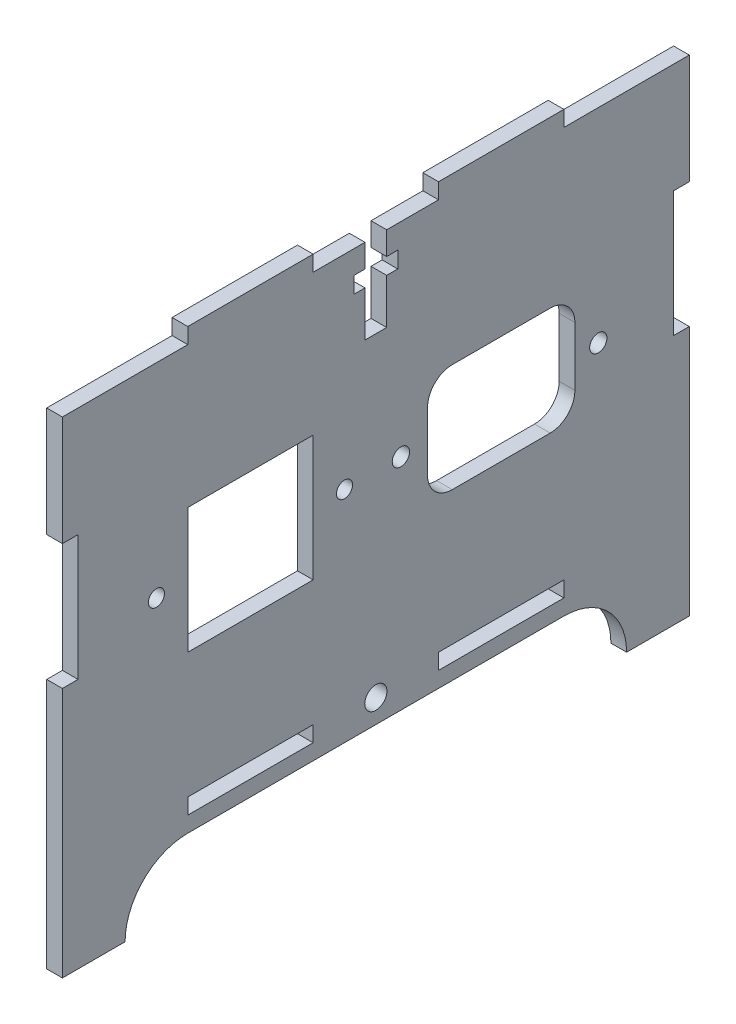
SolidWorks part; units mm, degrees
ref_plane "Front Plane" through (0, 0, 0) normal (0, 0, 1) x (1, 0, 0)
ref_plane "Top Plane" through (0, 0, 0) normal (0, 1, 0) x (1, 0, 0)
ref_plane "Right Plane" through (0, 0, 0) normal (1, 0, 0) x (0, 0, -1)
sketch "Sketch1" plane through (0, 0, 0) normal (1, 0, 0) x (0, 0, -1)
  line L1 (-63.5, 50.8) -> (63.5, 50.8)
  line L2 (-63.5, 50.8) -> (-63.5, -50.8)
  line L3 (-63.5, -50.8) -> (63.5, -50.8)
  line L4 (63.5, 50.8) -> (63.5, -50.8)
  line L5 (-63.5, 50.8) -> (63.5, -50.8) construction
  line L6 (-63.5, -50.8) -> (63.5, 50.8) construction
  point P0 (0, 0)
  dimension "D1" = 127
  dimension "D2" = 101.6
extrude "Boss-Extrude1" add sketch "Sketch1" along normal blind 3.175
sketch "Sketch2" plane through (3.175, 0, 0) normal (1, 0, 0) x (0, 0, -1)
  line L1 (-63.5, 50.8) -> (-38.1, 50.8)
  line L2 (-63.5, 50.8) -> (-63.5, 47.625)
  line L3 (-63.5, 47.625) -> (-38.1, 47.625)
  line L4 (-38.1, 50.8) -> (-38.1, 47.625)
  dimension "D1" = 25.4
  dimension "D2" = 3.175
extrude "Cut-Extrude1" cut sketch "Sketch2" against normal blind 6.35
pattern_linear "LPattern1" count 3 spacing 50.8 along (0, 0, -1) of "Cut-Extrude1"
sketch "Sketch5" plane through (3.175, 0, 0) normal (1, 0, 0) x (0, 0, -1)
  line L0 (-38.1, -50.8) -> (38.1, -50.8) construction
  line L1 (-63.5, -50.8) -> (63.5, -50.8) construction
  line L2 (-38.1, -38.1) -> (38.1, -38.1)
  line L3 (-38.1, -63.5) -> (38.1, -63.5)
  arc A0 (-38.1, -38.1) -> (-38.1, -63.5) centre (-38.1, -50.8) ccw
  arc A1 (38.1, -63.5) -> (38.1, -38.1) centre (38.1, -50.8) ccw
  point P4 (0, -50.8)
  dimension "D2" = 12.7
  dimension "D1" = 76.2
extrude "Cut-Extrude4" cut sketch "Sketch5" against normal blind 6.35
sketch "Sketch8" plane through (3.175, 0, 0) normal (1, 0, 0) x (0, 0, -1)
  line L0 (63.5, -50.8) -> (63.5, 47.625) construction
  line L1 (63.5, 25.4) -> (60.325, 25.4)
  line L2 (63.5, 25.4) -> (63.5, 0)
  line L3 (63.5, 0) -> (60.325, 0)
  line L4 (60.325, 25.4) -> (60.325, 0)
  line L5 (38.1, 50.8) -> (12.7, 50.8) construction
  dimension "D1" = 25.4
  dimension "D2" = 25.4
  dimension "D3" = 3.175
extrude "Cut-Extrude6" cut sketch "Sketch8" against normal blind 6.35
ref_plane "Plane1" through (0, 0, 0) normal (0, 0, 1) x (1, 0, 0)
sketch "Sketch9" plane through (0, 0, 0) normal (-1, 0, 0) x (0, 0, 1)
  line L0 (-63.5, -50.8) -> (-63.5, 0) construction
  line L1 (-38.1, -31.75) -> (-12.7, -31.75)
  line L2 (-38.1, -31.75) -> (-38.1, -34.925)
  line L3 (-38.1, -34.925) -> (-12.7, -34.925)
  line L4 (-12.7, -31.75) -> (-12.7, -34.925)
  line L5 (-38.1, 50.8) -> (-12.7, 50.8) construction
  point P6 (-25.4, 50.8)
  dimension "D1" = 25.4
  dimension "D2" = 3.175
  dimension "D3" = 25.4
  dimension "D4" = 82.55
extrude "Cut-Extrude7" cut sketch "Sketch9" against normal blind 6.35
pattern_linear "LPattern6" count 2 spacing 50.8 along (0, 0, 1) of "Cut-Extrude7"
sketch "Sketch16" plane through (0, 0, 0) normal (-1, 0, 0) x (0, 0, 1)
  line L0 (12.7, 47.625) -> (-12.7, 47.625) construction
  line L1 (-2.1971, 47.625) -> (2.1971, 47.625)
  line L2 (-2.1971, 47.625) -> (-2.1971, 30.48)
  line L3 (-2.1971, 30.48) -> (2.1971, 30.48)
  line L4 (2.1971, 47.625) -> (2.1971, 30.48)
  line L5 (-12.7, 47.625) -> (-12.7, 50.8) construction
  line L7 (-4.445, 42.926) -> (4.445, 42.926)
  line L8 (-4.445, 42.926) -> (-4.445, 39.624)
  line L9 (-4.445, 39.624) -> (4.445, 39.624)
  line L10 (4.445, 42.926) -> (4.445, 39.624)
  point P6 (0, 30.48)
  point P13 (0, 42.926)
  point P14 (4.445, 41.275)
  dimension "D1" = 4.3942
  dimension "D2" = 17.145
  dimension "D3" = 12.7
  dimension "D4" = 3.302
  dimension "D5" = 8.89
  dimension "D6" = 12.7
  dimension "D7" = 6.35
extrude "Cut-Extrude14" cut sketch "Sketch16" against normal blind 6.35 contours L7 L10 L9 L8 | L1 L4 L3 L2
hole_wizard "#8 Clearance Hole1" positions "Sketch18" profile "Sketch17" hole size "#8" standard "ANSI Inch"
sketch "Sketch18" plane through (0, 0, 0) normal (-1, 0, 0) x (0, 0, 1)
  line L3 (-12.7, -34.925) -> (-12.7, -31.75) construction
  line L4 (38.1, -31.75) -> (12.7, -31.75) construction
  point P0 (0, -33.3375)
  point P16 (-12.7, -33.3375)
  dimension "D1" = 12.7
  dimension "D2" = 1.5875
sketch "Sketch17" plane through (0, -33.3375, 0) normal (0, 1, 0) x (0, 0, 1)
  line L0 (0, 0) -> (0, 11.5107)
  line L1 (0, 11.5107) -> (2.2479, 10.16)
  line L2 (2.2479, 10.16) -> (2.2479, 0)
  line L5 (2.2479, 0) -> (0, 0)
  line L10 (0, 11.5107) -> (-2.2479, 10.16) construction
  line L11 (0, -6.35) -> (0, 107.95) construction
  dimension "Hole Dia." = 4.4958
  dimension "Hole Depth" = 10.16
  dimension "Drill Angle" = 118
sketch "Sketch19" plane through (0, 0, 0) normal (-1, 0, 0) x (0, 0, 1)
  line L0 (-49.53, 42.545) -> (-11.43, 42.545) construction
  line L1 (-49.53, 43.815) -> (-11.43, 43.815)
  line L2 (-49.53, 41.275) -> (-11.43, 41.275)
  line L3 (-38.1, 50.8) -> (-38.1, 47.625) construction
  line L4 (-2.1971, 47.625) -> (-12.7, 47.625) construction
  arc A0 (-49.53, 43.815) -> (-49.53, 41.275) centre (-49.53, 42.545) ccw
  arc A1 (-11.43, 41.275) -> (-11.43, 43.815) centre (-11.43, 42.545) ccw
  point P2 (-30.48, 42.545)
  point P7 (-30.48, 43.815)
  dimension "D2" = 1.27
  dimension "D1" = 38.1
  dimension "D3" = 7.62
  dimension "D4" = 3.81
extrude "Cut-Extrude15" [suppressed] cut sketch "Sketch19" against normal blind 6.35
mirror "Mirror2" [suppressed] about plane through (0, 0, 0) normal (0, 0, 1)
pattern_linear "LPattern7" [suppressed] count 5 spacing 5.08 of bodies 127
sketch "Sketch20" plane through (0, 0, 0) normal (-1, 0, 0) x (0, 0, 1)
  line L0 (-38.1, 50.8) -> (-12.7, 50.8) construction
  line L1 (-35.3225, 17.3101) -> (-15.4775, 17.3101)
  line L2 (-40.3225, 12.3101) -> (-40.3225, 0.3899)
  line L3 (-35.3225, -4.6101) -> (-15.4775, -4.6101)
  line L4 (-10.4775, 12.3101) -> (-10.4775, 0.3899)
  line L5 (-63.5, -50.8) -> (-63.5, 0) construction
  circle A0 centre (-45.0725, 6.35) radius 1.75
  circle A1 centre (-5.0725, 6.35) radius 1.75
  arc A2 (-40.3225, 0.3899) -> (-35.3225, -4.6101) centre (-35.3225, 0.3899) ccw
  arc A3 (-15.4775, 17.3101) -> (-10.4775, 12.3101) centre (-15.4775, 12.3101) cw
  arc A4 (-15.4775, -4.6101) -> (-10.4775, 0.3899) centre (-15.4775, 0.3899) ccw
  arc A5 (-40.3225, 12.3101) -> (-35.3225, 17.3101) centre (-35.3225, 12.3101) cw
  point P8 (-25.4, 17.3101)
  point P13 (-40.3225, 6.35)
  point P18 (-10.4775, 17.3101)
  point P21 (-10.4775, -4.6101)
  point P24 (-40.3225, 17.3101)
  dimension "D1" = 3.5
  dimension "D2" = 3.5
  dimension "D10" = 5
  dimension "D11" = 5
  dimension "D12" = 5
  dimension "D13" = 5
  dimension "D3" = 40
  dimension "D4" = 29.845
  dimension "D5" = 21.9202
  dimension "D6" = 38.1
  dimension "D7" = 44.45
extrude "Cut-Extrude16" cut sketch "Sketch20" against normal blind 7.62
sketch "Sketch25" plane through (0, 0, 0) normal (-1, 0, 0) x (0, 0, 1)
  line L0 (12.7, -31.75) -> (12.7, -34.925) construction
  line L1 (12.7, -6.35) -> (38.1, -6.35)
  line L2 (12.7, -6.35) -> (12.7, 19.05)
  line L3 (12.7, 19.05) -> (38.1, 19.05)
  line L4 (38.1, -6.35) -> (38.1, 19.05)
  line L6 (12.7, 50.8) -> (38.1, 50.8) construction
  point P6 (12.7, 6.35)
  dimension "D1" = 25.4
  dimension "D2" = 25.4
  dimension "D3" = 44.45
extrude "Cut-Extrude20" cut sketch "Sketch25" against normal blind 7.62
mirror "Mirror3" about plane through (0, 0, 0) normal (0, 0, 1) of "Cut-Extrude6"
hole_wizard "#4 Clearance Hole1" positions "Sketch27" profile "Sketch26" hole size "#4" standard "ANSI Inch"
sketch "Sketch27" plane through (3.175, 0, 0) normal (1, 0, 0) x (0, 0, -1)
  line L0 (-38.1, 19.05) -> (-38.1, -6.35) construction
  line L1 (-12.7, -6.35) -> (-12.7, 19.05) construction
  point P0 (-44.45, 6.35)
  point P2 (-6.35, 6.35)
  point P11 (-38.1, 6.35)
  point P12 (-12.7, 6.35)
  dimension "D1" = 6.35
  dimension "D2" = 6.35
sketch "Sketch26" plane through (3.175, 6.35, 44.45) normal (0, 1, 0) x (0, 0, -1)
  line L0 (0, 0) -> (0, 11.1406)
  line L1 (0, 11.1406) -> (1.6319, 10.16)
  line L2 (1.6319, 10.16) -> (1.6319, 0)
  line L5 (1.6319, 0) -> (0, 0)
  line L10 (0, 11.1406) -> (-1.6319, 10.16) construction
  line L11 (0, -6.35) -> (0, 107.95) construction
  dimension "Hole Dia." = 3.2639
  dimension "Hole Depth" = 10.16
  dimension "Drill Angle" = 118
